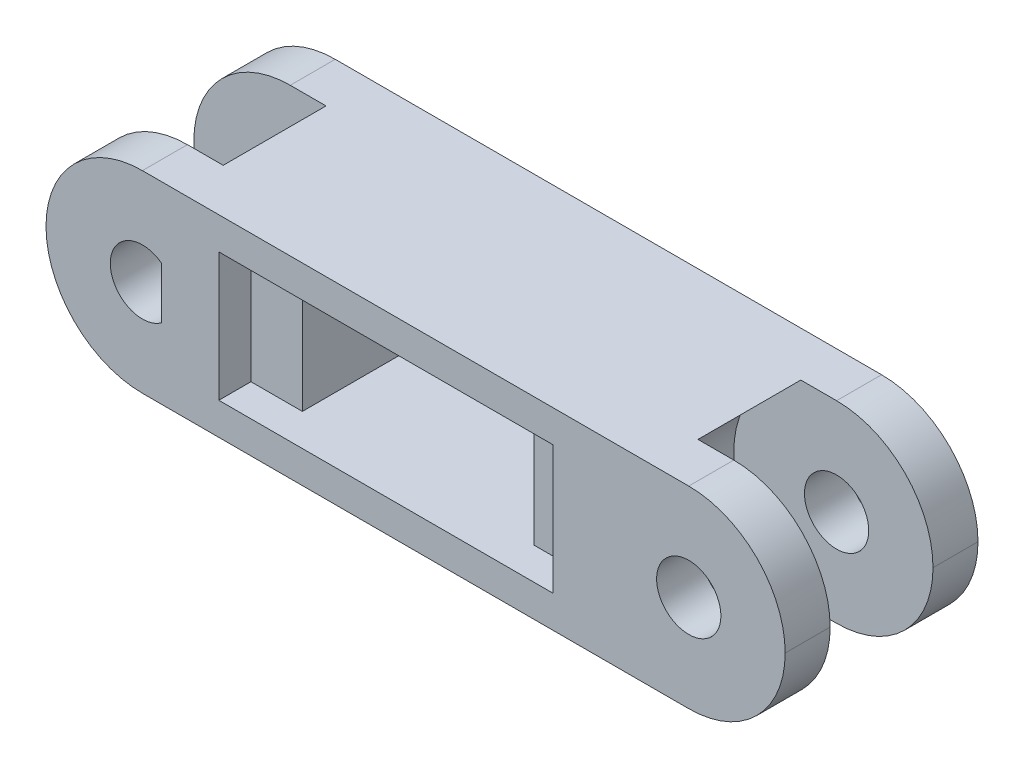
SolidWorks part; units mm, degrees
ref_plane "Front Plane" through (0, 0, 0) normal (0, 0, 1) x (1, 0, 0)
ref_plane "Top Plane" through (0, 0, 0) normal (0, 1, 0) x (1, 0, 0)
ref_plane "Right Plane" through (0, 0, 0) normal (1, 0, 0) x (0, 0, -1)
sketch "Sketch1" plane through (0, 0, 0) normal (0, 0, 1) x (1, 0, 0)
  line L1 (-31.75, -9.525) -> (31.75, -9.525)
  line L2 (-31.75, -9.525) -> (-31.75, 9.525)
  line L3 (-31.75, 9.525) -> (31.75, 9.525)
  line L4 (31.75, -9.525) -> (31.75, 9.525)
  line L5 (-31.75, -9.525) -> (31.75, 9.525) construction
  line L6 (-31.75, 9.525) -> (31.75, -9.525) construction
  point P0 (0, 0)
  dimension "D1" = 63.5
  dimension "D2" = 19.05
extrude "Boss-Extrude1" add sketch "Sketch1" along normal mid plane 19.05
fillet "Fillet1" radius 9.525 2 edges at (31.75, -9.525, 0) (31.75, 9.525, 0)
sketch "Sketch2" plane through (0, 0, 9.525) normal (0, 0, 1) x (1, 0, 0)
  circle A0 centre (22.225, 0) radius 3.175
  dimension "D1" = 6.35
extrude "Cut-Extrude1" cut sketch "Sketch2" against normal through all both and the other way through all
sketch "Sketch3" plane through (0, 0, 9.525) normal (0, 0, 1) x (1, 0, 0)
  line L0 (-7.6915, 0) -> (0, 0) construction
  line L1 (-24.2015, -6.35) -> (8.8185, -6.35)
  line L2 (-24.2015, -6.35) -> (-24.2015, 6.35)
  line L3 (-24.2015, 6.35) -> (8.8185, 6.35)
  line L4 (8.8185, -6.35) -> (8.8185, 6.35)
  line L5 (-24.2015, -6.35) -> (8.8185, 6.35) construction
  line L6 (-24.2015, 6.35) -> (8.8185, -6.35) construction
  point P0 (-7.6915, 0)
  point P8 (-7.6915, 0)
  dimension "D1" = 12.7
  dimension "D2" = 33.02
extrude "Cut-Extrude2" cut sketch "Sketch3" against normal blind 3.175 and the other way through all
sketch "Sketch6" plane through (0, 0, -9.525) normal (0, 0, -1) x (-1, 0, 0)
  line L1 (-3.7385, -6.35) -> (19.1215, -6.35)
  line L2 (-3.7385, -6.35) -> (-3.7385, 6.35)
  line L3 (-3.7385, 6.35) -> (19.1215, 6.35)
  line L4 (-8.8185, 6.35) -> (-8.8185, -6.35)
  line L5 (24.2015, 6.35) -> (-8.8185, 6.35)
  line L6 (24.2015, -6.35) -> (24.2015, 6.35)
  line L7 (-8.8185, -6.35) -> (24.2015, -6.35)
  line L8 (-8.8185, 6.35) -> (-8.8185, -6.35) construction
  line L9 (24.2015, 6.35) -> (-8.8185, 6.35) construction
  line L10 (24.2015, -6.35) -> (24.2015, 6.35) construction
  line L11 (-8.8185, -6.35) -> (24.2015, -6.35) construction
  line L12 (19.1215, -6.35) -> (19.1215, 6.35)
  line L13 (-3.7385, -6.35) -> (19.1215, 6.35) construction
  line L14 (-3.7385, 6.35) -> (19.1215, -6.35) construction
  point P2 (7.6915, 0)
  dimension "D2" = 5.08
  dimension "D3" = 22.86
  dimension "D1" = 0
extrude "Cut-Extrude4" cut sketch "Sketch6" against normal through all
sketch "Sketch7" plane through (0, 0, -9.525) normal (0, 0, -1) x (-1, 0, 0)
  line L4 (-3.7385, 6.35) -> (-8.8185, 6.35)
  line L5 (-3.7385, -6.35) -> (-3.7385, 6.35)
  line L6 (-8.8185, -6.35) -> (-3.7385, -6.35)
  line L7 (-8.8185, 6.35) -> (-8.8185, -6.35)
  line L8 (-3.7385, 6.35) -> (-8.8185, 6.35)
  line L9 (-3.7385, -6.35) -> (-3.7385, 6.35)
  line L10 (-8.8185, -6.35) -> (-3.7385, -6.35)
  line L11 (-8.8185, 6.35) -> (-8.8185, -6.35)
  dimension "D1" = 0
extrude "Cut-Extrude5" cut sketch "Sketch7" against normal offset from surface (9.525 mm away) 6.35 up to face at (6.2785, 0, 6.35)
sketch "Sketch8" plane through (0, 0, 9.525) normal (0, 0, 1) x (1, 0, 0)
  line L0 (-31.75, 9.525) -> (-31.75, -9.525) construction
  line L1 (-31.75, 9.525) -> (-31.75, -9.525)
  arc A0 (-31.75, 9.525) -> (-31.75, -9.525) centre (-31.75, 0) ccw
extrude "Boss-Extrude2" add sketch "Sketch8" against normal up to surface (19.05 mm away) up to face at (-5.1515, 0, -9.525)
sketch "Sketch9" plane through (0, 0, 9.525) normal (0, 0, 1) x (1, 0, 0)
  line L0 (-29.845, 2.54) -> (-29.845, -2.54)
  arc A0 (-29.845, 2.54) -> (-29.845, -2.54) centre (-31.75, 0) ccw
  dimension "D1" = 6.35
  dimension "D2" = 5.08
extrude "Cut-Extrude6" cut sketch "Sketch9" against normal through all
sketch "Sketch4" plane through (0, 0, 0) normal (0, 0, 1) x (1, 0, 0)
  circle A0 centre (22.225, 0) radius 10.16
  circle A1 centre (-31.75, 0) radius 10.16
  dimension "D1" = 20.32
  dimension "D2" = 20.32
extrude "Cut-Extrude3" cut sketch "Sketch4" against normal mid plane 10.16
